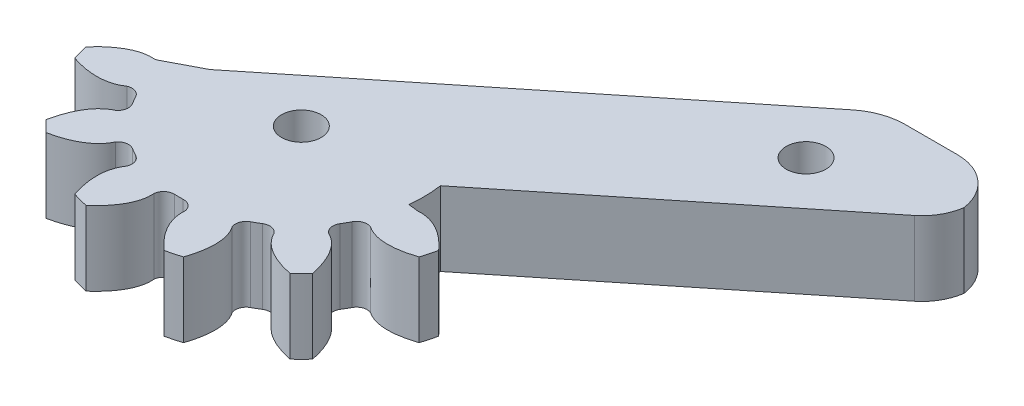
SolidWorks part; units mm, degrees
ref_plane "Plano frontal" through (0, 0, 0) normal (0, 0, 1) x (1, 0, 0)
ref_plane "Plano superior" through (0, 0, 0) normal (0, 1, 0) x (1, 0, 0)
ref_plane "Plano direito" through (0, 0, 0) normal (1, 0, 0) x (0, 0, -1)
ref_plane "Plano1" through (0, -6, 0) normal (0, -1, 0) x (1, 0, 0)
sketch "Esboço1" plane through (0, -6, 0) normal (0, -1, 0) x (1, 0, 0)
  line L0 (24.2604, -24.5) -> (28.5, -24.5)
  line L1 (31.006, -18.507) -> (9.7886, -1.4529)
  line L2 (9.8296, 1.143) -> (10.6232, 1.2352)
  line L3 (-10.4667, 1.2071) -> (-7.6421, -0.2724)
  line L4 (-7.6421, -0.2724) -> (21.1279, -23.3971)
  line L5 (0, 0) -> (0, -24.5) construction
  line L6 (0, 0) -> (22.5984, -18.1641) construction
  line L7 (14.3216, -17.9264) -> (20.5865, -10.1321) construction
  arc A0 (28.5, -24.5) -> (32.4603, -21.0624) centre (28.5, -20.5) ccw
  arc A1 (32.4603, -21.0624) -> (31.006, -18.507) centre (28.5, -21.6247) ccw
  arc A2 (9.7886, -1.4529) -> (9.8296, 1.143) centre (0, 0) ccw
  arc A3 (10.6232, 1.2352) -> (10.6525, 1.2391) centre (10.7505, 0.3832) cw
  arc A4 (14.2396, 3.1474) -> (13.9056, 4.3941) centre (0, 0) ccw
  arc A5 (9.8449, 4.2532) -> (8.7409, 4.6395) centre (9.5018, 5.0434) cw
  arc A6 (8.7409, 4.6395) -> (8.3883, 5.2501) centre (0, 0) ccw
  arc A7 (8.3883, 5.2501) -> (8.6058, 6.3993) centre (9.1186, 5.7071) cw
  arc A8 (10.7582, 9.8456) -> (9.8456, 10.7582) centre (0, 0) ccw
  arc A9 (6.3993, 8.6058) -> (5.2501, 8.3883) centre (5.7071, 9.1186) cw
  arc A10 (5.2501, 8.3883) -> (4.6395, 8.7409) centre (0, 0) ccw
  arc A11 (4.6395, 8.7409) -> (4.2532, 9.8449) centre (5.0434, 9.5018) cw
  arc A12 (4.3941, 13.9056) -> (3.1474, 14.2396) centre (0, 0) ccw
  arc A13 (1.2391, 10.6525) -> (0.3525, 9.8896) centre (0.3832, 10.7505) cw
  arc A14 (0.3525, 9.8896) -> (-0.3525, 9.8896) centre (0, 0) ccw
  arc A15 (-0.3525, 9.8896) -> (-1.2391, 10.6525) centre (-0.3832, 10.7505) cw
  arc A16 (-3.1474, 14.2396) -> (-4.3941, 13.9056) centre (0, 0) ccw
  arc A17 (-4.2532, 9.8449) -> (-4.6395, 8.7409) centre (-5.0434, 9.5018) cw
  arc A18 (-4.6395, 8.7409) -> (-5.2501, 8.3883) centre (0, 0) ccw
  arc A19 (-5.2501, 8.3883) -> (-6.3993, 8.6058) centre (-5.7071, 9.1186) cw
  arc A20 (-9.8456, 10.7582) -> (-10.7582, 9.8456) centre (0, 0) ccw
  arc A21 (-8.6058, 6.3993) -> (-8.3883, 5.2501) centre (-9.1186, 5.7071) cw
  arc A22 (-8.3883, 5.2501) -> (-8.7409, 4.6395) centre (0, 0) ccw
  arc A23 (-8.7409, 4.6395) -> (-9.8449, 4.2532) centre (-9.5018, 5.0434) cw
  arc A24 (-13.9056, 4.3941) -> (-14.2396, 3.1474) centre (0, 0) ccw
  arc A25 (-10.6525, 1.2391) -> (-10.4658, 1.1963) centre (-10.7505, 0.3832) cw
  arc A26 (-10.4658, 1.1963) -> (-10.4667, 1.2071) centre (-25, 0) ccw
  arc A27 (21.1279, -23.3971) -> (24.2604, -24.5) centre (24.2604, -19.5) ccw
  circle A28 centre (0, 0) radius 1.6
  circle A29 centre (22.5984, -18.1641) radius 1.6
  ellipse E0 centre (12.658, 10.7674) end of major axis (10.2742, 1.3033) minor radius 4.8741 (10.6525, 1.2391) -> (14.2396, 3.1474) ccw
  ellipse E1 centre (16.3459, -2.9959) end of major axis (9.5494, 4.0084) minor radius 4.8741 (13.9056, 4.3941) -> (9.8449, 4.2532) ccw
  ellipse E2 centre (5.5784, 15.6539) end of major axis (8.2461, 6.2658) minor radius 4.8741 (8.6058, 6.3993) -> (10.7582, 9.8456) ccw
  ellipse E3 centre (15.6539, 5.5784) end of major axis (25.0419, 2.9108) minor radius 4.8741 (9.8456, 10.7582) -> (6.3993, 8.6058) ccw
  ellipse E4 centre (-2.9959, 16.3459) end of major axis (4.0084, 9.5494) minor radius 4.8741 (4.2532, 9.8449) -> (4.3941, 13.9056) ccw
  ellipse E5 centre (10.7674, 12.658) end of major axis (20.2316, 15.0418) minor radius 4.8741 (3.1474, 14.2396) -> (1.2391, 10.6525) ccw
  ellipse E6 centre (-10.7674, 12.658) end of major axis (-1.3033, 10.2742) minor radius 4.8741 (-1.2391, 10.6525) -> (-3.1474, 14.2396) ccw
  ellipse E7 centre (2.9959, 16.3459) end of major axis (10.0002, 23.1424) minor radius 4.8741 (-4.3941, 13.9056) -> (-4.2532, 9.8449) ccw
  ellipse E8 centre (-15.6539, 5.5784) end of major axis (-6.2658, 8.2461) minor radius 4.8741 (-6.3993, 8.6058) -> (-9.8456, 10.7582) ccw
  ellipse E9 centre (-5.5784, 15.6539) end of major axis (-2.9108, 25.0419) minor radius 4.8741 (-10.7582, 9.8456) -> (-8.6058, 6.3993) ccw
  ellipse E10 centre (-16.3459, -2.9959) end of major axis (-23.1424, -10.0002) minor radius 4.8741 (-9.8449, 4.2532) -> (-13.9056, 4.3941) ccw
  ellipse E11 centre (-12.658, 10.7674) end of major axis (-15.0418, 20.2316) minor radius 4.8741 (-14.2396, 3.1474) -> (-10.6525, 1.2391) ccw
  point P12 (12.658, 10.7674)
  point P13 (17.3844, 9.577)
  point P14 (10.2742, 1.3033)
  point P15 (10.6525, 1.2391)
  point P16 (14.2396, 3.1474)
  point P17 (12.6372, 1.7684)
  point P18 (12.6789, 19.7665)
  point P26 (16.3459, -2.9959)
  point P27 (19.8439, 0.3983)
  point P28 (9.5494, 4.0084)
  point P29 (13.9056, 4.3941)
  point P30 (9.8449, 4.2532)
  point P31 (11.8283, 4.7871)
  point P32 (20.8634, -10.7788)
  point P44 (5.5784, 15.6539)
  point P45 (10.2669, 16.9861)
  point P46 (8.2461, 6.2658)
  point P47 (8.6058, 6.3993)
  point P48 (10.7582, 9.8456)
  point P49 (10.0599, 7.8501)
  point P50 (1.097, 23.4577)
  point P58 (15.6539, 5.5784)
  point P59 (25.0419, 2.9108)
  point P60 (16.9861, 10.2669)
  point P61 (9.8456, 10.7582)
  point P62 (6.3993, 8.6058)
  point P63 (7.8501, 10.0599)
  point P64 (23.4577, 1.097)
  point P76 (-2.9959, 16.3459)
  point P77 (4.0084, 9.5494)
  point P78 (-6.3901, 12.8479)
  point P79 (4.2532, 9.8449)
  point P80 (4.3941, 13.9056)
  point P81 (4.7871, 11.8283)
  point P82 (-10.7788, 20.8634)
  point P90 (10.7674, 12.658)
  point P91 (20.2316, 15.0418)
  point P92 (9.577, 17.3844)
  point P93 (3.1474, 14.2396)
  point P94 (1.2391, 10.6525)
  point P95 (1.7684, 12.6372)
  point P96 (19.7665, 12.6789)
  point P108 (-10.7674, 12.658)
  point P109 (-1.3033, 10.2742)
  point P110 (-11.9579, 7.9316)
  point P111 (-1.2391, 10.6525)
  point P112 (-3.1474, 14.2396)
  point P113 (-1.7684, 12.6372)
  point P114 (-19.7665, 12.6789)
  point P122 (2.9959, 16.3459)
  point P123 (10.0002, 23.1424)
  point P124 (-0.3983, 19.8439)
  point P125 (-4.3941, 13.9056)
  point P126 (-4.2532, 9.8449)
  point P127 (-4.7871, 11.8283)
  point P128 (10.7788, 20.8634)
  point P140 (-15.6539, 5.5784)
  point P141 (-6.2658, 8.2461)
  point P142 (-14.3216, 0.89)
  point P143 (-6.3993, 8.6058)
  point P144 (-9.8456, 10.7582)
  point P145 (-7.8501, 10.0599)
  point P146 (-23.4577, 1.097)
  point P154 (-5.5784, 15.6539)
  point P155 (-0.89, 14.3216)
  point P156 (-2.9108, 25.0419)
  point P157 (-10.7582, 9.8456)
  point P158 (-8.6058, 6.3993)
  point P159 (-10.0599, 7.8501)
  point P160 (-1.097, 23.4577)
  point P172 (-16.3459, -2.9959)
  point P173 (-12.8479, -6.3901)
  point P174 (-23.1424, -10.0002)
  point P175 (-9.8449, 4.2532)
  point P176 (-13.9056, 4.3941)
  point P177 (-11.8283, 4.7871)
  point P178 (-20.8634, -10.7788)
  point P186 (-12.658, 10.7674)
  point P187 (-7.9316, 11.9579)
  point P188 (-15.0418, 20.2316)
  point P189 (-14.2396, 3.1474)
  point P190 (-10.6525, 1.2391)
  point P191 (-12.6372, 1.7684)
  point P192 (-12.6789, 19.7665)
  point P212 (17.4541, -14.0293)
  point P213 (0, 0)
  point P214 (26.3802, -24.5)
  point P215 (0, 0)
  dimension "D2" = 4
  dimension "D3" = 5
  dimension "D5" = 3.2
  dimension "D1" = 10
  dimension "D4" = 28.9935
  dimension "D6" = 51.208
  dimension "D7" = 6.3359
  dimension "D8" = 2.8982
  dimension "D9" = 9.8619
extrude "Ressalto-extrusão1" add sketch "Esboço1" against normal blind 6
